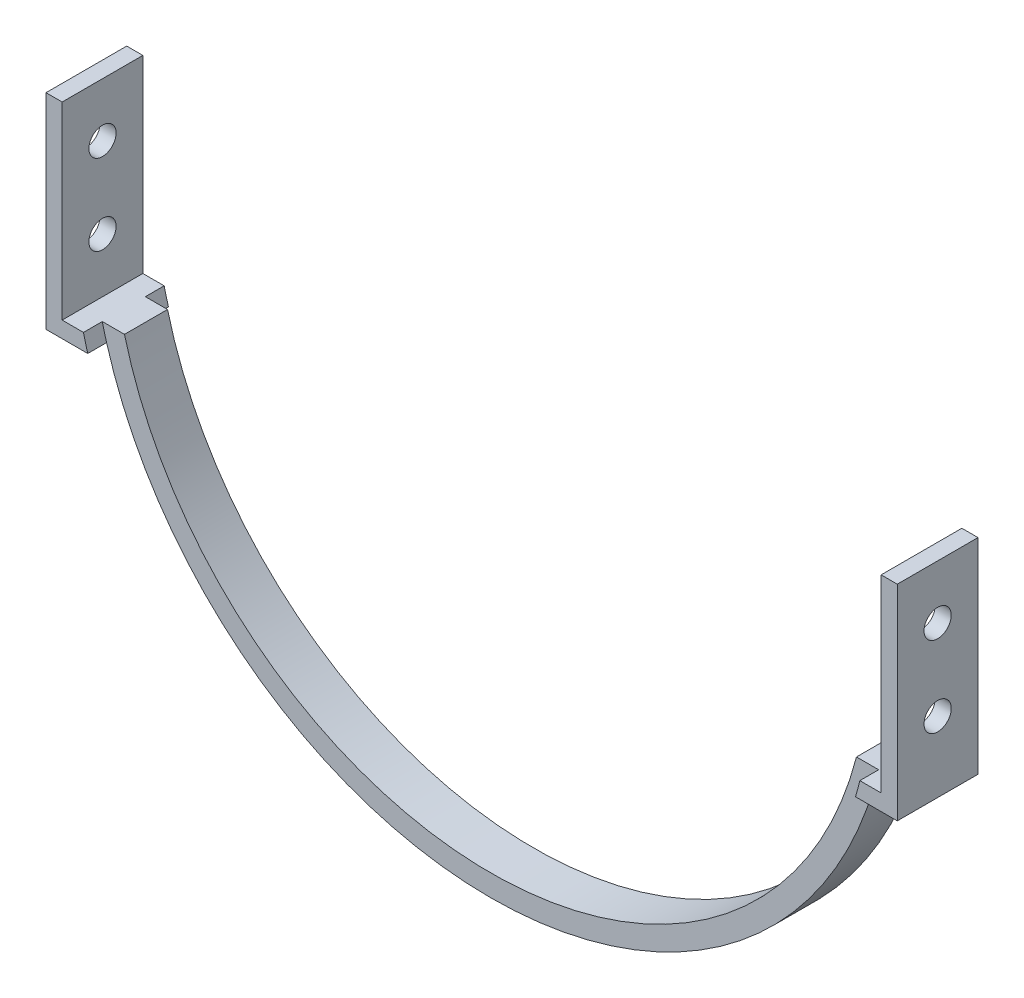
SolidWorks part; units mm, degrees
ref_plane "Front Plane" through (0, 0, 0) normal (0, 0, 1) x (1, 0, 0)
ref_plane "Top Plane" through (0, 0, 0) normal (0, 1, 0) x (1, 0, 0)
ref_plane "Right Plane" through (0, 0, 0) normal (1, 0, 0) x (0, 0, -1)
sketch "Sketch1" plane through (0, 0, 0) normal (0, 0, 1) x (1, 0, 0)
  line L0 (-72.1391, -17.6) -> (-76.1, -17.6)
  line L1 (-76, 0) -> (-70.255, 0) construction
  line L2 (-70.255, 0) -> (70.255, 0) construction
  line L3 (76, 0) -> (74.255, 0) construction
  line L5 (-76, 0) -> (-76, -17.5) construction
  line L6 (-76, 0) -> (-76, 17.5) construction
  line L7 (-76, 17.5) -> (-70.255, 17.5) construction
  line L8 (-70.255, 17.5) -> (-70.255, 0) construction
  line L9 (-76, -17.5) -> (-72.1634, -17.5) construction
  line L11 (0, 0) -> (0, -70.255) construction
  line L12 (70.255, 17.5) -> (70.255, 0) construction
  line L13 (72.1634, 17.5) -> (70.255, 17.5)
  line L14 (76, 0) -> (76, 17.5) construction
  line L15 (76, 0) -> (76, -17.5) construction
  line L16 (76, -17.5) -> (72.1634, -17.5) construction
  line L17 (70.255, 0) -> (76, 0) construction
  line L18 (-70.255, 17.5) -> (-68.0405, 17.5) construction
  line L19 (-68.0405, 17.5) -> (68.0405, 17.5) construction
  line L20 (68.0405, 17.5) -> (70.255, 17.5) construction
  line L21 (-72.1634, -17.5) -> (-68.0405, -17.5) construction
  line L22 (-68.0405, -17.5) -> (68.0405, -17.5) construction
  line L23 (68.0405, -17.5) -> (72.1634, -17.5) construction
  line L24 (-76.1, -17.6) -> (-76.1, 17.5)
  line L25 (-76.1, 17.5) -> (-79.1, 17.5)
  line L26 (-79.1, 17.5) -> (-79.1, -20.6)
  line L27 (-79.1, -20.6) -> (-71.3403, -20.6)
  line L28 (-76.1, -17.5) -> (-76, -17.5) construction
  line L29 (-76, -17.5) -> (-76, -17.6) construction
  line L30 (-76, -17.6) -> (-76, -20.6) construction
  line L31 (-76.1, -17.5) -> (-79.1, -17.5) construction
  line L32 (72.1391, -17.6) -> (76.1, -17.6)
  line L33 (79.1, -20.6) -> (71.3403, -20.6)
  line L34 (76.1, -17.6) -> (76.1, 17.5)
  line L35 (79.1, 17.5) -> (79.1, -20.6)
  line L36 (76.1, 17.5) -> (79.1, 17.5)
  line L37 (76, 17.5) -> (72.1634, 17.5) construction
  line L38 (72.1391, -17.6) -> (68.0147, -17.6)
  line L39 (-72.1391, -17.6) -> (-68.0147, -17.6)
  arc A0 (-68.0147, -17.6) -> (68.0147, -17.6) centre (0, 0) ccw
  arc A1 (-72.1634, -17.5) -> (-72.1391, -17.6) centre (0, 0) ccw construction
  arc A2 (74.255, 0) -> (-74.255, 0) centre (0, 0) ccw construction
  arc A3 (68.0405, 17.5) -> (-68.0405, 17.5) centre (0, 0) ccw construction
  arc A4 (-74.255, 0) -> (-73.7302, -8.8123) centre (0, 0) ccw construction
  arc A5 (-73.7302, -8.8123) -> (-72.1634, -17.5) centre (0, 0) ccw construction
  arc A6 (73.7302, -8.8123) -> (74.255, 0) centre (0, 0) ccw construction
  arc A7 (72.1634, -17.5) -> (73.7302, -8.8123) centre (0, 0) ccw construction
  arc A8 (-68.0405, 17.5) -> (-70.255, 0) centre (0, 0) ccw construction
  arc A9 (70.255, 0) -> (68.0405, 17.5) centre (0, 0) ccw construction
  arc A10 (-70.255, 0) -> (-68.0405, -17.5) centre (0, 0) ccw construction
  arc A11 (-71.3403, -20.6) -> (71.3403, -20.6) centre (0, 0) ccw
  arc A12 (-72.1391, -17.6) -> (-71.3403, -20.6) centre (0, 0) ccw
  arc A13 (68.0405, -17.5) -> (70.255, 0) centre (0, 0) ccw construction
  arc A14 (72.1391, -17.6) -> (72.1634, -17.5) centre (0, 0) ccw construction
  arc A15 (71.3403, -20.6) -> (72.1391, -17.6) centre (0, 0) ccw
  arc A16 (68.0147, -17.6) -> (68.0405, -17.5) centre (0, 0) ccw construction
  arc A17 (-68.0405, -17.5) -> (-68.0147, -17.6) centre (0, 0) ccw construction
  point P12 (-73.1275, 17.5)
  dimension "D1" = 140.51
  dimension "D2" = 4
  dimension "D3" = 76
  dimension "D4" = 35
  dimension "D5" = 0.1
  dimension "D6" = 3
  dimension "D7" = 3
extrude "Boss-Extrude1" add sketch "Sketch1" along normal mid plane 8 contours A8 L18 L7 L6 L5 L9 L21 A0 | L21 A1 L23 A0 | A9 A0 L23 L16 L15 L14 L13 L20 region at (-70.0769, -19.15, 0)
ref_plane "Plane1" through (70.255, 0, 0) normal (-1, 0, 0) x (0, 0, 1)
extrude "Boss-Extrude2" add sketch "Sketch1<5>" along normal mid plane 15 contours A12 L0 L24 L25 L26 L27 | A15 L33 L35 L36 L34 L32 region at (-77.2229, -3.3528, 0) region at (77.2229, -3.3528, 0)
sketch "Sketch1<5>" plane through (0, 0, 0) normal (0, 0, 1) x (1, 0, 0) same geometry as "Sketch1"
sketch "Sketch2" plane through (-79.1, 0, 0) normal (-1, 0, 0) x (0, 0, 1)
  line L0 (0, 17.5) -> (0, 7.5) construction
  line L1 (7.5, 17.5) -> (-7.5, 17.5) construction
  line L2 (0, 7.5) -> (0, -7.5) construction
  line L3 (0, -7.5) -> (0, -17.5) construction
  line L6 (0, -17.5) -> (0, -20.6) construction
  line L7 (7.5, -20.6) -> (-7.5, -20.6) construction
  point P10 (0, 7.5)
  point P11 (0, -7.5)
  dimension "D1" = 15
  dimension "D2" = 3.1
hole_wizard "#8 (0.199) Diameter Hole1" positions "3DSketch2" profile "Sketch4" hole size "#8" standard "ANSI Inch"
sketch3d "3DSketch2"
  point P0 (-79.1, 7.5, 0)
  point P3 (-79.1, -7.5, 0)
sketch "Sketch4" plane through (-79.1, 7.5, 0) normal (0, 1, 0) x (0, 0, 1)
  line L0 (0, 0) -> (0, 13)
  line L1 (0, 13) -> (2.5273, 11.4814)
  line L2 (2.5273, 11.4814) -> (2.5273, 0)
  line L5 (2.5273, 0) -> (0, 0)
  line L10 (0, 13) -> (-2.5273, 11.4814) construction
  line L11 (0, -6.35) -> (0, 107.95) construction
  dimension "Hole Dia." = 5.0546
  dimension "Hole Depth" = 13
  dimension "Drill Angle" = 118
mirror "Mirror1" about plane through (0, 0, 0) normal (1, 0, 0) of "#8 (0.199) Diameter Hole1"
